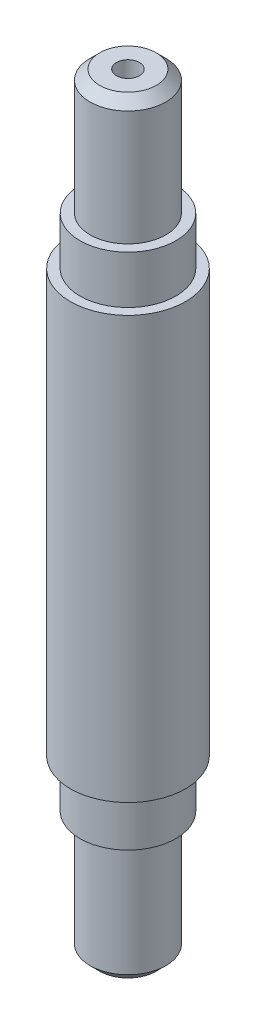
SolidWorks part; units mm, degrees
ref_plane "Front Plane" through (0, 0, 0) normal (0, 0, 1) x (1, 0, 0)
ref_plane "Top Plane" through (0, 0, 0) normal (0, 1, 0) x (1, 0, 0)
ref_plane "Right Plane" through (0, 0, 0) normal (1, 0, 0) x (0, 0, -1)
sketch "Sketch4" plane through (0, 0, 0) normal (0, 1, 0) x (1, 0, 0)
  circle A0 centre (0, 0) radius 3.95
  circle A1 centre (0, 0) radius 1.2
  circle A2 centre (0, 0) radius 5
  circle A3 centre (0, 0) radius 6
  dimension "D1" = 7.9
  dimension "D2" = 2.4
  dimension "D3" = 10
  dimension "D4" = 12
extrude "Boss-Extrude2" add sketch "Sketch4" along normal blind 18 contours A0 A1 | A1 region at (-3.8383, 0, 0) region at (0, 0, 0)
extrude "Cut-Extrude2" cut sketch "Sketch4<3>" along normal blind 2.5 from offset 15.5 contours A1 region at (0, 0, 0)
sketch "Sketch4<3>" plane through (0, 0, 0) normal (0, 1, 0) x (1, 0, 0) same geometry as "Sketch4"
extrude "Boss-Extrude3" add sketch "Sketch4<4>" along normal blind 5 contours A2 A0 region at (-4.8586, 0, 0)
sketch "Sketch4<4>" plane through (0, 0, 0) normal (0, 1, 0) x (1, 0, 0) same geometry as "Sketch4"
extrude "Boss-Extrude4" add sketch "Sketch4<5>" against normal blind 44 contours A1 | A0 A1 | A2 A0 | A3 A2 region at (-3.8383, 0, 0) region at (0, 0, 0) region at (-4.8586, 0, 0) region at (-5.8303, 0, 0)
sketch "Sketch4<5>" plane through (0, 0, 0) normal (0, 1, 0) x (1, 0, 0) same geometry as "Sketch4"
extrude "Boss-Extrude8" add sketch "Sketch4<10>" against normal blind 49 contours A1 | A0 A1 | A2 A0 region at (-3.8383, 0, 0) region at (0, 0, 0) region at (-4.8586, 0, 0)
sketch "Sketch4<10>" plane through (0, 0, 0) normal (0, 1, 0) x (1, 0, 0) same geometry as "Sketch4"
extrude "Boss-Extrude9" add sketch "Sketch4<11>" against normal blind 62 contours A1 | A0 A1 region at (-3.8383, 0, 0) region at (0, 0, 0)
sketch "Sketch4<11>" plane through (0, 0, 0) normal (0, 1, 0) x (1, 0, 0) same geometry as "Sketch4"
extrude "Cut-Extrude3" cut sketch "Sketch4<13>" against normal through all from offset 59.5 contours A1 region at (0, 0, 0) offset against normal yes
sketch "Sketch4<13>" plane through (0, 0, 0) normal (0, 1, 0) x (1, 0, 0) same geometry as "Sketch4"
chamfer "Chamfer3" distance 1 angle 45 2 edges at (0, 18, 3.95) (0, -62, 3.95)
